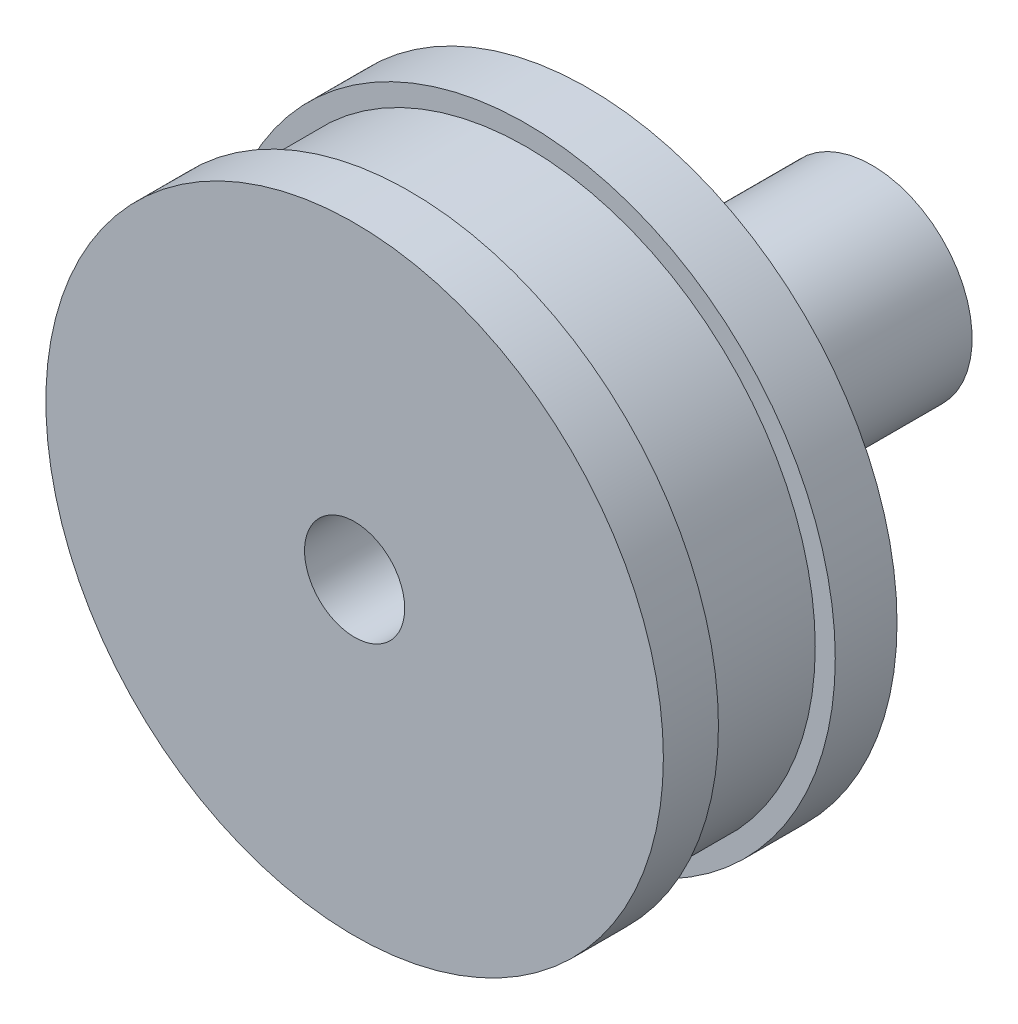
SolidWorks part; units mm, degrees
ref_plane "前视基准面" through (0, 0, 0) normal (0, 0, 1) x (1, 0, 0)
ref_plane "上视基准面" through (0, 0, 0) normal (0, 1, 0) x (1, 0, 0)
ref_plane "右视基准面" through (0, 0, 0) normal (1, 0, 0) x (0, 0, -1)
sketch "草图1" plane through (0, 0, 0) normal (0, 0, 1) x (1, 0, 0)
  circle A0 centre (0, 0) radius 18.5
  circle A2 centre (0, 0) radius 3
extrude "凸台-拉伸1" add sketch "草图1" along normal blind 14
ref_plane "基准面4" through (0, 0, 7.7) normal (0, 0, 1) x (1, 0, 0)
sketch "草图2" plane through (0, 0, 7.7) normal (0, 0, 1) x (1, 0, 0)
  circle A0 centre (0, 0) radius 17.3
  circle A1 centre (0, 0) radius 18.5
extrude "切除-拉伸1" cut sketch "草图2" against normal blind 2.2
extrude "切除-拉伸2" cut sketch "草图2<2>" along normal blind 0.8
sketch "草图2<2>" plane through (0, 0, 7.7) normal (0, 0, 1) x (1, 0, 0) same geometry as "草图2"
extrude "切除-拉伸3" cut sketch "草图2<4>" against normal blind 4
sketch "草图2<4>" plane through (0, 0, 7.7) normal (0, 0, 1) x (1, 0, 0) same geometry as "草图2"
extrude "切除-拉伸5" cut sketch "草图2<6>" along normal blind 3
sketch "草图2<6>" plane through (0, 0, 7.7) normal (0, 0, 1) x (1, 0, 0) same geometry as "草图2"
sketch "草图3" plane through (0, 0, 0) normal (0, 0, -1) x (-1, 0, 0)
  circle A0 centre (0, 0) radius 7
extrude "凸台-拉伸3" add sketch "草图3" along normal blind 5
sketch "草图4" plane through (0, 0, -5) normal (0, 0, -1) x (-1, 0, 0)
  circle A0 centre (0, 0) radius 6
  dimension "D1" = 12
extrude "凸台-拉伸4" add sketch "草图4" along normal blind 12
